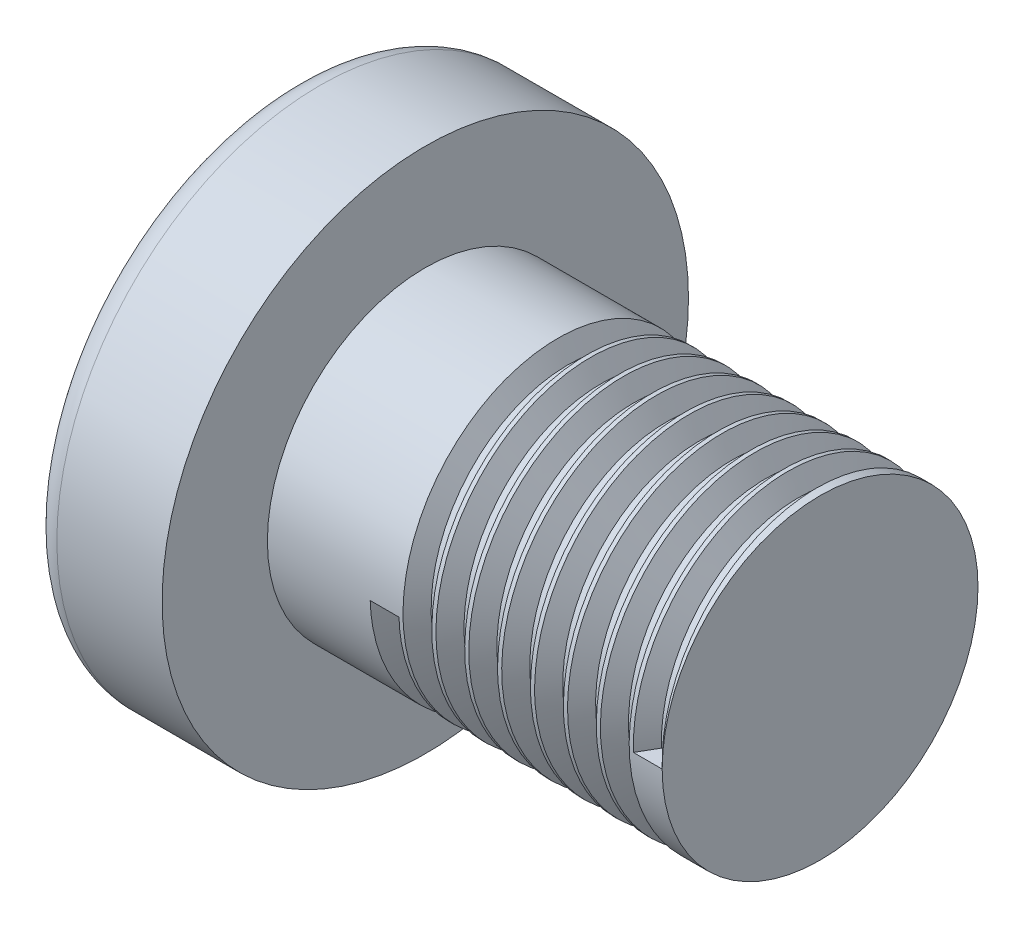
SolidWorks part; units mm, degrees
ref_plane "Front Plane" through (0, 0, 0) normal (0, 0, 1) x (1, 0, 0)
ref_plane "Top Plane" through (0, 0, 0) normal (0, 1, 0) x (1, 0, 0)
ref_plane "Right Plane" through (0, 0, 0) normal (1, 0, 0) x (0, 0, -1)
sketch "Sketch1" plane through (0, 0, 0) normal (0, 0, 1) x (1, 0, 0)
  line L0 (0, 0) -> (0, 10)
  line L1 (0, 10) -> (5, 10)
  line L2 (5, 10) -> (5, 6)
  line L3 (5, 6) -> (20, 6)
  line L4 (20, 6) -> (20, 0)
  line L5 (20, 0) -> (0, 0)
  dimension "D1" = 20
  dimension "D2" = 6
  dimension "D3" = 10
  dimension "D4" = 5
revolve "Revolve1" add sketch "Sketch1" angle 360 about L5
sketch "Sketch2" plane through (0, 0, 0) normal (-1, 0, 0) x (0, 0, 1)
  line L1 (5.7735, 0) -> (2.8868, 5)
  line L2 (2.8868, 5) -> (-2.8868, 5)
  line L3 (-2.8868, 5) -> (-5.7735, 0)
  line L4 (-5.7735, 0) -> (-2.8868, -5)
  line L5 (-2.8868, -5) -> (2.8868, -5)
  line L6 (2.8868, -5) -> (5.7735, 0)
  circle A0 centre (0, 0) radius 5 construction
  dimension "D1" = 10
extrude "Cut-Extrude1" cut sketch "Sketch2" against normal blind 5
fillet "Fillet1" radius 1 1 edges at (0, 0, -10)
thread "Thread1" pitch 1.25 method cut profile "Thread Profile1" start angle 0, offset 0, length 10, pitch 1.25, diameter 12
ref_plane "Plane1" through (20, 0, 6) normal (0, -1, 0) x (0, 0, 1)
sketch "Thread Profile1" plane through (20, 0, 6) normal (0, -1, 0) x (0, 0, 1)
  line L0 (0, 0) -> (0, 1.25) construction
  line L11 (0, 0) -> (0, 1.0937)
  line L12 (0, 1.0937) -> (-0.6766, 0.7031)
  line L13 (-0.6766, 0.7031) -> (-0.6766, 0.3906)
  line L15 (-0.6766, 0.3906) -> (0, 0)
  line L17 (-0.6766, 0.5469) -> (0, 0.5469) construction
  point P2 (0, 0)
  dimension "Pitch" = 1.25
  dimension "Profile_Angle" = 60
  dimension "Profile_Land" = 0.3125
  dimension "Profile_Height" = 0.6766
